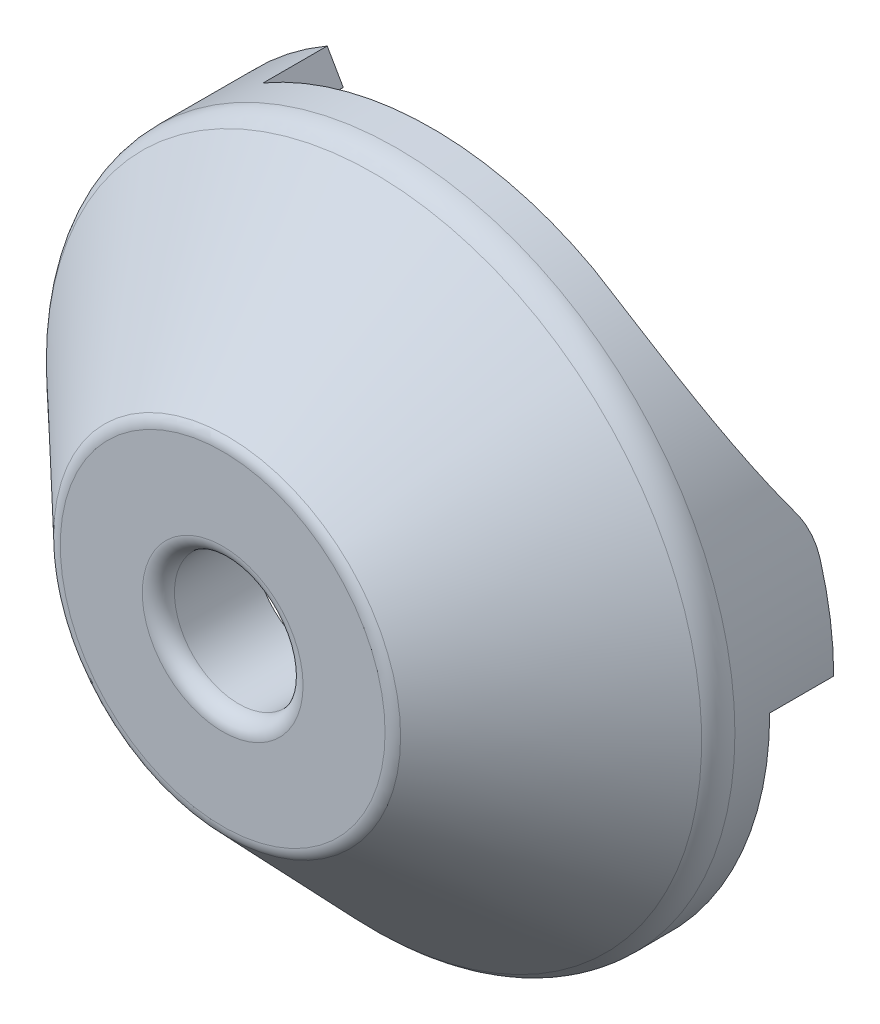
SolidWorks part; units mm, degrees
other "Objet de détail1"
ref_plane "Plan1" through (0, 0, 0) normal (0, 0, 1) x (1, 0, 0)
ref_plane "Plan2" through (0, 0, 0) normal (0, 1, 0) x (1, 0, 0)
ref_plane "Plan3" through (0, 0, 0) normal (1, 0, 0) x (0, 0, -1)
sketch "Esquisse1" plane through (0, 0, 0) normal (0, 0, 1) x (1, 0, 0)
  circle A0 centre (0, 0) radius 4
  circle A1 centre (0, 0) radius 5
  dimension "D1" = 8
  dimension "D2" = 10
extrude "Base-Extrusion" add sketch "Esquisse1" along normal blind 4
sketch "Esquisse2" plane through (0, 0, 4) normal (0, 0, 1) x (1, 0, 0)
  circle A0 centre (0, 0) radius 10.5
  circle A1 centre (0, 0) radius 4
  dimension "D1" = 21
  dimension "D2" = 8
extrude "Boss.-Extru.1" add sketch "Esquisse2" along normal blind 2
ref_axis "Axe1" through (0, 0, -50) along (0, 0, 1)
sketch "Esquisse3" plane through (0, 0, 0) normal (0, 1, 0) x (1, 0, 0)
  line L0 (-10.5, -6) -> (-20.3793, 3.4089)
  line L1 (-10.5, -6) -> (10.5, -6) construction
  line L2 (-21, 6) -> (-21, 4.8571)
  line L3 (10.5, -4) -> (-10.5, -4) construction
  line L4 (-21, 6) -> (-21, 11)
  line L5 (-10.5, -6) -> (-10.5, -4)
  line L6 (-10.5, -4) -> (-18.4293, 4.101)
  line L7 (-21, 11) -> (-19, 11)
  line L8 (-19, 11) -> (-19, 5.5)
  line L9 (0, 19.0621) -> (0, -10) construction
  line L10 (0, -4) -> (0, 0) construction
  arc A0 (-21, 4.8571) -> (-20.3793, 3.4089) centre (-19, 4.8571) ccw
  arc A1 (-18.4293, 4.101) -> (-19, 5.5) centre (-17, 5.5) cw
  point P15 (-21, 4)
  dimension "D6" = 2
  dimension "D1" = 21
  dimension "D2" = 4
  dimension "D3" = 2
  dimension "D4" = 2
  dimension "D5" = 7
  dimension "D7" = 5.5
  dimension "D8" = 8.101
revolve "Boss.-Révol.1" add sketch "Esquisse3" angle 360 about L9
sketch "Esquisse4" plane through (0, 0, 0) normal (0, 1, 0) x (1, 0, 0)
  line L0 (11.0033, 7.0201) -> (23.5958, 7.0201)
  line L1 (23.5958, 7.0201) -> (23.5958, 11.0201)
  arc A0 (23.5958, 11.0201) -> (11.0033, 7.0201) centre (10, 32) ccw
  dimension "D3" = 50
  dimension "D1" = 32
  dimension "D2" = 10
  dimension "D4" = 12.5925
  dimension "D5" = 4
extrude "Enlèv. mat.-Extru.1" cut sketch "Esquisse4" against normal through all
pattern_circular "Répétition circulaire1" count 3 every 120 about axis through (0, 0, -50) along (0, 0, 1) of "Enlèv. mat.-Extru.1"
fillet "Congé1" radius 5 3 edges at (-15.2601, 12.9266, -11) (-3.5647, -19.6789, -11) (18.8248, 6.7524, -11)
fillet "Congé2" radius 1 2 edges at (-10.5, 0, 6) (4, 0, 6)
